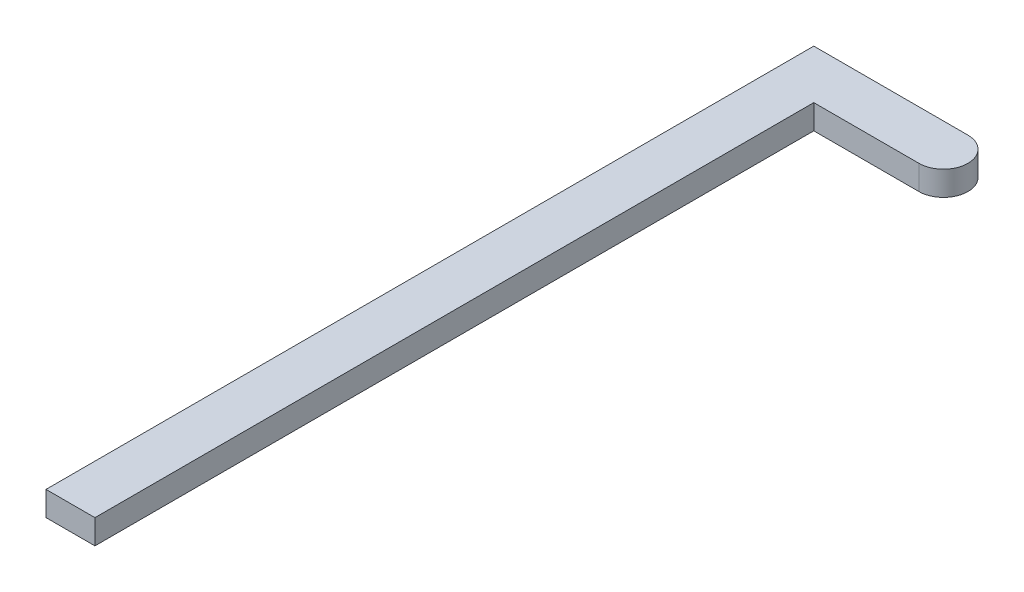
SolidWorks part; units mm, degrees
material "6061 Alloy"
ref_plane "Front Plane" through (0, 0, 0) normal (0, 0, 1) x (1, 0, 0)
ref_plane "Top Plane" through (0, 0, 0) normal (0, 1, 0) x (1, 0, 0)
ref_plane "Right Plane" through (0, 0, 0) normal (1, 0, 0) x (0, 0, -1)
sketch "Sketch1" plane through (0, 0, 0) normal (0, 1, 0) x (1, 0, 0)
  line L0 (0, 0) -> (-33.65, 0) construction
  line L1 (-33.65, 0) -> (-33.65, -192.896) construction
  line L2 (0, 6.35) -> (-40, 6.35)
  line L3 (-40, 6.35) -> (-40, -192.896)
  line L4 (0, -6.35) -> (-27.3, -6.35)
  line L5 (-27.3, -6.35) -> (-27.3, -192.896)
  line L6 (-40, -192.896) -> (-27.3, -192.896)
  arc A0 (0, 6.35) -> (0, -6.35) centre (0, 0) cw
  dimension "D1" = 192.896
  dimension "D2" = 40
  dimension "D3" = 6.35
  dimension "D4" = 6.35
extrude "Boss-Extrude1" add sketch "Sketch1" along normal blind 6.35
